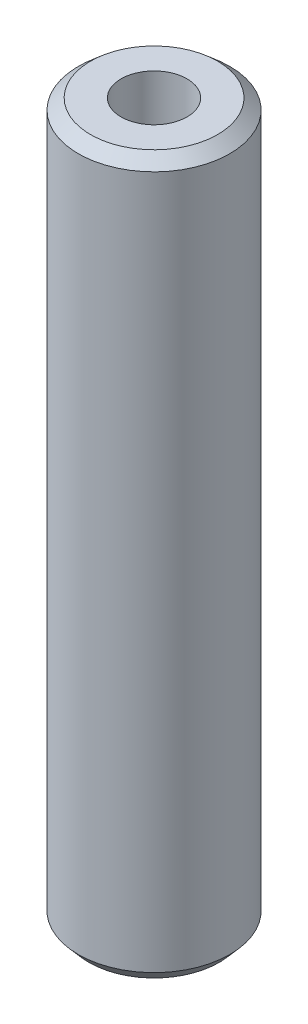
SolidWorks part; units mm, degrees
ref_plane "Front Plane" through (0, 0, 0) normal (0, 0, 1) x (1, 0, 0)
ref_plane "Top Plane" through (0, 0, 0) normal (0, 1, 0) x (1, 0, 0)
ref_plane "Right Plane" through (0, 0, 0) normal (1, 0, 0) x (0, 0, -1)
sketch "Sketch1" plane through (0, 0, 0) normal (0, 1, 0) x (1, 0, 0)
  circle A0 centre (0, 0) radius 22.5
  dimension "SHAFT_OD" = 45
extrude "Boss-Extrude1" add sketch "Sketch1" along normal blind 212.8022
sketch "Sketch2" plane through (0, 0, 0) normal (0, 1, 0) x (1, 0, 0)
  circle A0 centre (0, 0) radius 9.8074
  dimension "BORE_D" = 19.6148
extrude "Cut-Extrude1" cut sketch "Sketch2" along normal through all
chamfer "Chamfer1" distance 3.1335 angle 48.991 2 edges at (0, 212.8022, 22.5) (0, 0, 22.5) first distance on face at (0, 212.8022, 22.5) first distance on face at (0, 0, 9.8074)
